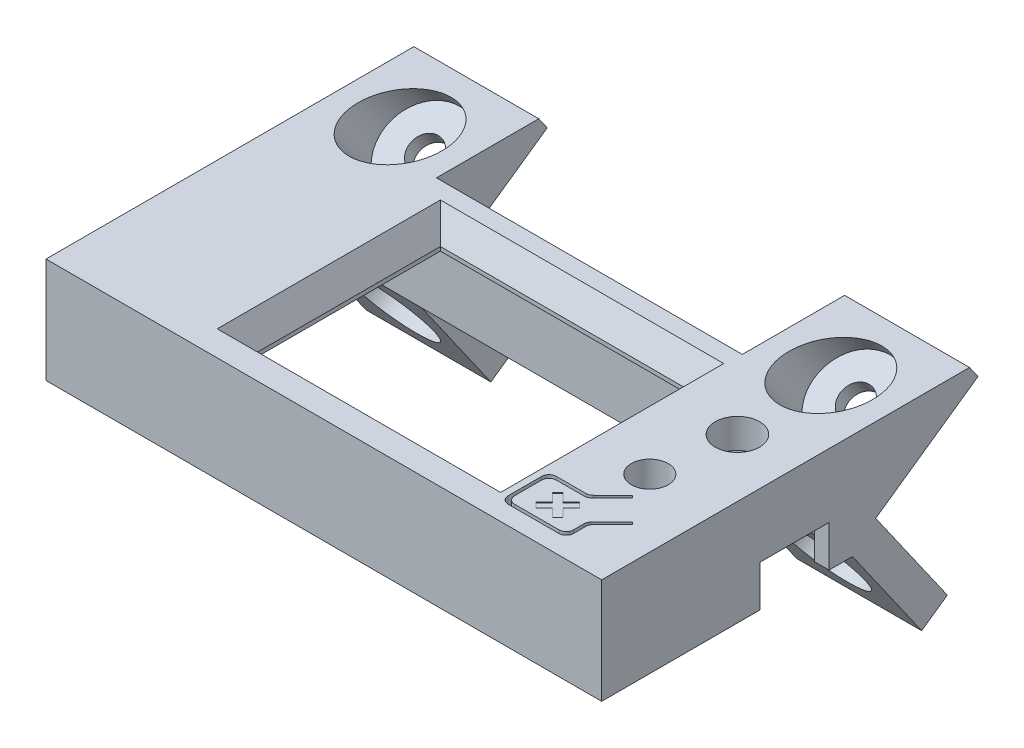
SolidWorks part; units mm, degrees
ref_plane "Front Plane" through (0, 0, 0) normal (0, 0, 1) x (1, 0, 0)
ref_plane "Top Plane" through (0, 0, 0) normal (0, 1, 0) x (1, 0, 0)
ref_plane "Right Plane" through (0, 0, 0) normal (1, 0, 0) x (0, 0, -1)
sketch "Sketch1" plane through (0, 0, 0) normal (0, 1, 0) x (1, 0, 0)
  line L0 (-53.5, 16.0718) -> (-53.5, 24)
  line L1 (-52.5, 23) -> (52.5, 23) construction
  line L2 (-52.5, 23) -> (-52.5, -23) construction
  line L3 (-52.5, -23) -> (52.5, -23) construction
  line L4 (52.5, 23) -> (52.5, -23) construction
  line L5 (-52.5, 23) -> (52.5, -23) construction
  line L6 (-52.5, -23) -> (52.5, 23) construction
  line L7 (-50.4, -20.575) -> (50.4, -20.575) construction
  line L8 (-50.4, -20.575) -> (-50.4, 20.575) construction
  line L9 (-50.4, 20.575) -> (50.4, 20.575) construction
  line L10 (50.4, -20.575) -> (50.4, 20.575) construction
  line L11 (-50.4, -20.575) -> (50.4, 20.575) construction
  line L12 (-50.4, 20.575) -> (50.4, -20.575) construction
  line L13 (-53.5, 24) -> (53.5, 24)
  line L14 (-53.5, 24) -> (-53.5, -24)
  line L15 (-53.5, -24) -> (53.5, -24)
  line L16 (53.5, 24) -> (53.5, -24)
  line L17 (-53.5, 24) -> (53.5, -24) construction
  line L18 (-53.5, -24) -> (53.5, 24) construction
  line L19 (-56.5, 27) -> (56.5, 27)
  line L20 (-56.5, 27) -> (-56.5, -27)
  line L21 (-56.5, -27) -> (56.5, -27)
  line L22 (56.5, 27) -> (56.5, -27)
  line L23 (-56.5, 27) -> (56.5, -27) construction
  line L24 (-56.5, -27) -> (56.5, 27) construction
  line L25 (-53.5, 24) -> (-45.5718, 24)
  line L26 (-53.5, -16.0718) -> (-53.5, -24)
  line L27 (-45.5718, -24) -> (-53.5, -24)
  line L28 (45.5718, -24) -> (53.5, -24)
  line L29 (53.5, -24) -> (53.5, -16.0718)
  line L30 (53.5, 16.0718) -> (53.5, 24)
  line L31 (53.5, 24) -> (45.5718, 24)
  line L32 (44.8283, -22.5373) -> (32.8283, -22.5373)
  line L33 (-31.4, 22.5) -> (29.82, 22.5) construction
  line L34 (-31.4, 22.5) -> (-31.4, -20.88) construction
  line L35 (-31.4, -20.88) -> (29.82, -20.88) construction
  line L36 (29.82, 22.5) -> (29.82, -20.88) construction
  line L37 (-23.8, 20.5) -> (27.82, 20.5)
  line L38 (-23.8, 20.5) -> (-23.8, -18.88)
  line L39 (-23.8, -18.88) -> (27.82, -18.88)
  line L40 (27.82, 20.5) -> (27.82, -18.88)
  line L41 (32.8283, -22.5373) -> (32.8283, -14.0373)
  line L42 (32.8283, -14.0373) -> (40.5857, -14.0373)
  line L43 (40.5857, -14.0373) -> (45.1819, -9.4411)
  line L44 (45.1819, -9.4411) -> (49.4245, -13.6837) construction
  line L45 (49.4245, -13.6837) -> (44.8283, -18.2799)
  line L46 (44.8283, -18.2799) -> (44.8283, -22.5373)
  line L47 (39.04, -19.31) -> (32.8283, -22.5373) construction
  line L48 (40.5857, -14.0373) -> (44.8283, -18.2799) construction
  circle A0 centre (-50.4, 20.575) radius 1.5
  circle A1 centre (-50.4, -20.575) radius 1.5
  circle A2 centre (50.4, -20.575) radius 1.5
  circle A3 centre (50.4, 20.575) radius 1.5
  arc A4 (-45.5718, 24) -> (-53.5, 16.0718) centre (-52.5, 23) cw
  arc A5 (-53.5, -16.0718) -> (-45.5718, -24) centre (-52.5, -23) cw
  arc A6 (45.5718, 24) -> (53.5, 16.0718) centre (52.5, 23) ccw
  arc A7 (53.5, -16.0718) -> (45.5718, -24) centre (52.5, -23) ccw
  circle A8 centre (39.04, -19.31) radius 1.5 construction
  circle A9 centre (42.78, -3.495) radius 3.75
  circle A10 centre (44.69, 12.41) radius 4.5
  point P0 (0, 0)
  point P5 (0, 0)
  point P15 (0, 0)
  point P20 (0, 0)
  dimension "D3" = 3
  dimension "D4" = 100.8
  dimension "D5" = 41.15
  dimension "D6" = 1
  dimension "D10" = 106.426
  dimension "D11" = 7
  dimension "D12" = 83.9
  dimension "D13" = 106.426
  dimension "D14" = 22.68
  dimension "D21" = 3
  dimension "D22" = 7.5
  dimension "D23" = 9
  dimension "D30" = 6
  dimension "D1" = 46
  dimension "D2" = 105
  dimension "D7" = 1
  dimension "D8" = 3
  dimension "D9" = 3
  dimension "D15" = 43.38
  dimension "D16" = 45.5
  dimension "D17" = 2
  dimension "D18" = 2
  dimension "D19" = 2
  dimension "D20" = 7.6
  dimension "D24" = 9.72
  dimension "D25" = 26.495
  dimension "D26" = 7.81
  dimension "D27" = 10.59
  dimension "D28" = 13.46
  dimension "D29" = 3.69
  dimension "D31" = 135
  dimension "D32" = 12
  dimension "D33" = 8.5
  dimension "D34" = 6.5
  dimension "D35" = 7
  dimension "D36" = 27.454
extrude "Boss-Extrude1" add sketch "Sketch1" against normal blind 10 contours L22 L19 L20 L21 L13 L16 L15 L14 L0 region at (0, 0, -25.7476)
extrude "Boss-Extrude2" add sketch "Sketch1<3>" along normal blind 5.4 contours L22 L19 L20 L21 L13 L16 L15 L14 L0 | A4 L13 L0 A0 | A5 L14 L15 A1 | L13 A6 L16 A3 | L16 A7 L15 A2 region at (-53.3869, 0, -20.0359) region at (-47.6303, 0, 18.1303) region at (49.5359, 0, -23.8869) region at (47.6303, 0, 18.1303) region at (0, 0, -25.7476)
sketch "Sketch1<3>" plane through (0, 0, 0) normal (0, 1, 0) x (1, 0, 0) same geometry as "Sketch1"
extrude "Boss-Extrude5" add sketch "Sketch1<4>" along normal blind 6 from surface contours L22 L19 L20 L21 L13 L16 L15 L14 L0 | A4 L13 L0 A0 | A5 L14 L15 A1 | A0 | A1 | A2 | L16 A7 L15 A2 | L13 A6 L16 A3 | A3 | A7 L16 A6 L13 A4 L14 A5 L15 A10 A9 L37 L40 L39 L38 L45 L46 L32 L41 L42 L43 L44 | L46 L45 L44 L43 L42 L41 L32 region at (-46.721, 0, -17.221) region at (-53.3869, 0, -20.0359) region at (-47.6303, 0, 18.1303) region at (49.5359, 0, -23.8869) region at (47.6303, 0, 18.1303) region at (0, 0, -25.7476) region at (-50.4, 0, -20.575) region at (-50.4, 0, 20.575) region at (50.4, 0, 20.575) region at (50.4, 0, -20.575) starting at face at (0, 5.4, 0)
sketch "Sketch1<4>" plane through (0, 0, 0) normal (0, 1, 0) x (1, 0, 0) same geometry as "Sketch1"
extrude "Cut-Extrude-Thin1" cut sketch "Sketch1<5>" along normal up to surface (11.4 mm away) from surface thin contours L45 L46 L32 L41 L42 L43 up to face at (44.69, 11.4, -7.91) starting at face at (42.78, 5.4, 7.245) thin type one direction reverse wall 0.65
sketch "Sketch1<5>" plane through (0, 0, 0) normal (0, 1, 0) x (1, 0, 0) same geometry as "Sketch1"
sketch "Sketch2" plane through (0, 5.4, 0) normal (0, -1, 0) x (1, 0, 0)
  line L0 (32.8283, 14.0373) -> (32.8283, 22.5373)
  line L1 (32.8283, 22.5373) -> (44.8283, 22.5373)
  line L2 (44.8283, 22.5373) -> (44.8283, 18.2799)
  line L3 (44.8283, 18.2799) -> (49.4245, 13.6837)
  line L4 (49.4245, 13.6837) -> (45.1819, 9.4411)
  line L5 (45.1819, 9.4411) -> (40.5857, 14.0373)
  line L6 (40.5857, 14.0373) -> (32.8283, 14.0373)
extrude "Cut-Extrude1" cut sketch "Sketch2" against normal offset from surface (5 mm away) 1 up to face at (41.4815, 11.4, 16.384)
fillet "Fillet1" radius 1.5 10 edges at (44.8283, 10.9, 18.2799) (45.4783, 8.4, 18.5491) (40.3164, 8.4, 13.3873) (40.5857, 10.9, 14.0373) (32.1783, 8.4, 13.3873) (32.8283, 10.9, 14.0373) (32.8283, 10.9, 22.5373) (32.1783, 8.4, 23.1873) (44.8283, 10.9, 22.5373) (45.4783, 8.4, 23.1873)
sketch "Sketch3" plane through (0, 11.4, 0) normal (0, 1, 0) x (1, 0, 0)
  line L0 (32.8283, -14.0373) -> (32.8283, -22.5373) construction
  line L1 (34.3283, -22.5373) -> (43.3283, -22.5373) construction
  line L2 (44.8283, -22.5373) -> (32.8283, -22.5373) construction
  line L3 (32.8283, -15.5373) -> (32.8283, -21.0373) construction
  line L4 (32.8283, -14.0373) -> (44.8283, -14.0373) construction
  line L5 (44.8283, -14.0373) -> (44.8283, -22.5373) construction
  line L6 (32.8283, -14.0373) -> (44.8283, -22.5373) construction
  line L7 (37.139, -15.5373) -> (38.8283, -17.2266)
  line L8 (41.5783, -15.5373) -> (36.0783, -15.5373) construction
  line L9 (41.5783, -15.5373) -> (41.5783, -21.0373) construction
  line L10 (41.5783, -21.0373) -> (36.0783, -21.0373) construction
  line L11 (36.0783, -15.5373) -> (36.0783, -21.0373) construction
  line L12 (41.5783, -15.5373) -> (36.0783, -21.0373) construction
  line L13 (41.5783, -21.0373) -> (36.0783, -15.5373) construction
  line L14 (38.8283, -17.2266) -> (40.5177, -15.5373)
  line L15 (40.5177, -15.5373) -> (41.5783, -16.5979)
  line L16 (41.5783, -16.5979) -> (39.889, -18.2873)
  line L17 (39.889, -18.2873) -> (41.5783, -19.9766)
  line L18 (41.5783, -19.9766) -> (40.5177, -21.0373)
  line L19 (40.5177, -21.0373) -> (38.8283, -19.3479)
  line L20 (38.8283, -19.3479) -> (37.139, -21.0373)
  line L21 (37.139, -21.0373) -> (36.0783, -19.9766)
  line L22 (36.0783, -19.9766) -> (37.7677, -18.2873)
  line L23 (37.7677, -18.2873) -> (36.0783, -16.5979)
  line L24 (36.0783, -16.5979) -> (37.139, -15.5373)
  point P3 (32.8283, -18.2873)
  point P6 (38.8283, -22.5373)
  point P8 (38.8283, -22.5373)
  point P11 (32.8283, -18.2873)
  point P12 (38.8283, -18.2873)
  dimension "D1" = 5.5
  dimension "D2" = 1.5
  dimension "D3" = 45
extrude "Cut-Extrude2" cut sketch "Sketch3" against normal blind 0.2 contours L7 L14 L15 L16 L17 L18 L19 L20 L21 L22 L23 L24
chamfer "Chamfer1" distance 3 angle 60 4 edges at (2.01, 11.4, 18.88) (27.82, 11.4, -0.81) (-23.8, 11.4, -0.81) (2.01, 11.4, -20.5) first distance on face at (40.6267, 11.4, 17.0722)
sketch "Sketch4" plane through (-56.5, 0, 0) normal (-1, 0, 0) x (0, 0, 1)
  line L0 (-23, 0) -> (23, 0)
  line L1 (-23, -1.6) -> (23, -1.6) construction
  line L2 (-23, 0) -> (-23, -1.6) construction
  line L3 (23, 0) -> (23, -1.6) construction
  line L5 (-11.35, -1.6) -> (15.14, -1.6)
  line L6 (-11.35, -1.6) -> (-11.35, -5.6)
  line L7 (-11.35, -5.6) -> (15.14, -5.6)
  line L8 (15.14, -1.6) -> (15.14, -5.6)
  dimension "D1" = 1.6
  dimension "D2" = 34.35
  dimension "D3" = 7.86
  dimension "D4" = 4
extrude "Cut-Extrude3" cut sketch "Sketch4" against normal blind 5 contours L8 L5 L6 L7 region at (-56.5, -3.6, 1.895)
sketch "Sketch5" plane through (56.5, 0, 0) normal (1, 0, 0) x (0, 0, -1)
  line L0 (-23, 0) -> (23, 0) construction
  line L1 (23, 0) -> (23, -1.6) construction
  line L2 (23, -1.6) -> (-23, -1.6) construction
  line L3 (-23, -1.6) -> (-23, 0) construction
  line L4 (27, -10) -> (-27, -10) construction
  line L5 (19.23, -1.6) -> (5.23, -1.6)
  line L6 (19.23, -1.6) -> (19.23, -10)
  line L7 (19.23, -10) -> (5.23, -10)
  line L8 (5.23, -1.6) -> (5.23, -10)
  point P10 (0, 0)
  point P11 (5.23, -6.9407)
  dimension "D1" = 1.6
  dimension "D3" = 3.77
  dimension "D4" = 17.77
extrude "Cut-Extrude4" cut sketch "Sketch5" against normal blind 5
sketch "Sketch6" plane through (56.5, 0, 0) normal (1, 0, 0) x (0, 0, -1)
  line L1 (47.8065, 11.4) -> (49.5272, 8.9425)
  line L2 (49.5272, 8.9425) -> (28.7207, -5.6263)
  line L3 (28.7207, -5.6263) -> (43.2896, -26.4328)
  line L4 (43.2896, -26.4328) -> (38.0669, -30.0897)
  line L5 (38.0669, -30.0897) -> (24, -10)
  line L6 (24, -10) -> (27, -10)
  line L7 (27, -10) -> (27, 11.4) construction
  line L8 (27, -10) -> (27, -3.1688)
  line L9 (28.7207, -5.6263) -> (27, -3.1688) construction
  line L11 (47.8065, 11.4) -> (27, 11.4)
  line L12 (27, -3.1688) -> (27, 11.4)
  point P3 (50.2659, 8.9425)
  line M14 (27, -10) -> (27, 11.4)
  dimension "D1" = 145
  dimension "D2" = 25.4
  dimension "D3" = 3
  dimension "D4" = 3
  dimension "D5" = 3
extrude "Boss-Extrude6" add sketch "Sketch6" against normal blind 25.4 contours L9 L2 L1 L11 M14 | L3 L9 L6 L5 L4 M14 region at (56.5, 5.3203, -35.3835) region at (56.5, -17.9819, -33.6009)
sketch "Sketch7" plane through (0, -17.2696, -12.0923) normal (0, -0.8192, -0.5736) x (1, 0, 0)
  line L0 (56.5, -45.6995) -> (31.1, -20.2995) construction
  circle A0 centre (43.8, -32.9995) radius 3.25
  circle A1 centre (43.8, -32.9995) radius 8.5
  dimension "D1" = 6.5
  dimension "D2" = 17
sketch "Sketch8" plane through (0, 11.6433, -16.6284) normal (0, 0.5736, -0.8192) x (-1, 0, 0)
  line L0 (-56.5, -21.0823) -> (-31.1, -46.4823) construction
  circle A0 centre (-43.8, -33.7823) radius 3.25
  circle A2 centre (-43.8, -33.7823) radius 8.5
  dimension "D1" = 6.5
  dimension "D2" = 17
extrude "Cut-Extrude5" cut sketch "Sketch7" against normal through all contours A0
extrude "Cut-Extrude8" cut sketch "Sketch7<4>" against normal through all from offset 3 offset against normal yes
sketch "Sketch7<4>" plane through (0, -17.2696, -12.0923) normal (0, -0.8192, -0.5736) x (1, 0, 0) same geometry as "Sketch7"
extrude "Cut-Extrude6" cut sketch "Sketch8" against normal through all contours A0
extrude "Cut-Extrude9" cut sketch "Sketch8<5>" against normal blind 25.4 from offset 3 offset against normal yes
sketch "Sketch8<5>" plane through (0, 11.6433, -16.6284) normal (0, 0.5736, -0.8192) x (-1, 0, 0) same geometry as "Sketch8"
sketch "Sketch9" plane through (31.1, 0, 0) normal (-1, 0, 0) x (0, 0, 1)
  line L0 (-27, 11.4) -> (-35.5658, -0.8333)
  line L1 (-49.5272, 8.9425) -> (-28.7207, -5.6263) construction
  line L2 (-35.5658, -0.8333) -> (-27, -6.8312)
  line L3 (-27, -10) -> (-27, 11.4) construction
  line L4 (-27, -6.8312) -> (-27, 11.4)
mirror "Mirror1" about plane through (0, 0, 0) normal (1, 0, 0) of "Cut-Extrude5", "Boss-Extrude6", "Cut-Extrude9", "Cut-Extrude6", "Cut-Extrude8"
extrude "Boss-Extrude9" add sketch "Sketch9" along normal up to surface (62.2 mm away)
